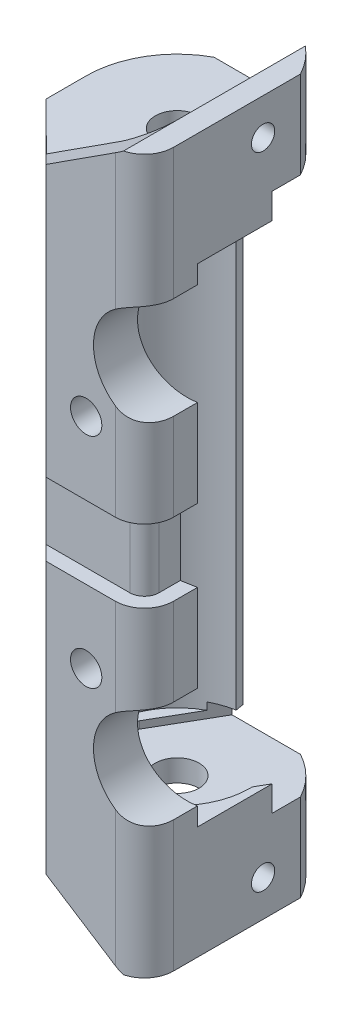
SolidWorks part; units mm, degrees
ref_plane "前视基准面" through (0, 0, 0) normal (0, 0, 1) x (1, 0, 0)
ref_plane "上视基准面" through (0, 0, 0) normal (0, 1, 0) x (1, 0, 0)
ref_plane "右视基准面" through (0, 0, 0) normal (1, 0, 0) x (0, 0, -1)
other "Configuration Table"
sketch "草图1" plane through (0, 0, 0) normal (0, 1, 0) x (1, 0, 0)
  line L0 (0, 12.5) -> (11, 12.5)
  line L1 (11, 12.5) -> (11, 10)
  line L3 (0, 10) -> (11, 10)
  line L6 (10, 0) -> (11, 0)
  line L7 (11, 0) -> (11, -5.9372)
  arc A0 (0, 10) -> (0, -10) centre (0, 0) ccw
  arc A1 (0, 12.5) -> (0, -12.5) centre (0, 0) ccw
  arc A2 (0, -12.5) -> (11, -5.9372) centre (0, 0) ccw
  arc A3 (0, -10) -> (10, 0) centre (0, 0) ccw
  dimension "D1" = 20
  dimension "D2" = 2.5
  dimension "D3" = 11
extrude "凸台-拉伸1" add sketch "草图1" along normal blind 80
sketch "草图2" plane through (0, 80, 0) normal (0, 1, 0) x (1, 0, 0)
  line L0 (-1.7365, 9.8481) -> (-2.1706, 12.3101)
  line L1 (0, 12.5) -> (0, 0) construction
  line L2 (0, 10) -> (11, 10) construction
  line L3 (11, 10) -> (11, 12.5) construction
  line L4 (11, 12.5) -> (0, 12.5) construction
  line L5 (0, 10) -> (11, 10)
  line L6 (11, 10) -> (11, 12.5)
  line L7 (11, 12.5) -> (0, 12.5)
  arc A0 (0, 10) -> (10, 0) centre (0, 0) ccw construction
  arc A1 (0, 12.5) -> (11, -5.9372) centre (0, 0) ccw construction
  arc A2 (0, 10) -> (-1.7365, 9.8481) centre (0, 0) ccw
  arc A3 (0, 12.5) -> (-2.1706, 12.3101) centre (0, 0) ccw
  dimension "D1" = 10
extrude "切除-拉伸1" cut sketch "草图2" against normal up to next
sketch "草图3" plane through (0, 80, 0) normal (0, 1, 0) x (1, 0, 0)
  line L0 (11, -5.9372) -> (11, 0) construction
  line L1 (-3.5, 12) -> (11, 12)
  line L2 (-3.5, 12) -> (-3.5, 12.5)
  line L3 (-3.5, 12.5) -> (11, 12.5)
  line L4 (11, 12) -> (11, 12.5)
  arc A0 (-2.1706, 12.3101) -> (11, -5.9372) centre (0, 0) ccw construction
  dimension "D1" = 12
extrude "切除-拉伸3" cut sketch "草图3" against normal up to next contours L1 L4 L3 L2
sketch "草图4" plane through (11, 0, 0) normal (1, 0, 0) x (0, 0, -1)
  line L0 (0, 0) -> (0, 89) construction
  line L1 (-5.9372, 80) -> (5.9372, 80)
  line L2 (-5.9372, 80) -> (-5.9372, 89)
  line L3 (-5.9372, 89) -> (5.9372, 89)
  line L4 (5.9372, 80) -> (5.9372, 89)
  line L5 (-12.5, 40) -> (12, 40) construction
  line L6 (-12.5, 80) -> (-12.5, 0) construction
  line L7 (12, 80) -> (12, 0) construction
  line L8 (5.9372, 0) -> (5.9372, -9)
  line L9 (-5.9372, -9) -> (5.9372, -9)
  line L10 (-5.9372, 0) -> (-5.9372, -9)
  line L11 (-5.9372, 0) -> (5.9372, 0)
  circle A0 centre (0.8, 84) radius 1.6
  circle A1 centre (0.8, -4) radius 1.6
  dimension "D2" = 3.2
  dimension "D3" = 88
  dimension "D4" = 0.8
  dimension "D1" = 98
extrude "凸台-拉伸2" add sketch "草图4" against normal blind 3
sketch "草图6" plane through (0, 0, 0) normal (0.9848, 0, -0.1736) x (-0.1736, 0, -0.9848)
  line L1 (-10, 73.5) -> (12.1851, 73.5)
  line L2 (-10, 73.5) -> (-10, 6.5)
  line L3 (-10, 6.5) -> (12.1851, 6.5)
  line L4 (12.1851, 73.5) -> (12.1851, 6.5)
  line L5 (12.1851, 80) -> (12.1851, 0) construction
  line L6 (-12.5, 40) -> (12.1851, 40) construction
  line L7 (-12.5, 80) -> (-12.5, 0) construction
  line L8 (10, 0) -> (10, 80) construction
  dimension "D1" = 67
  dimension "D2" = 20
extrude "切除-拉伸4" cut sketch "草图6" along normal up to next
sketch "草图7" plane through (8, 0, 0) normal (-1, 0, 0) x (0, 0, 1)
  circle A0 centre (-0.8, 84) radius 4 construction
  dimension "D1" = 8
sketch "草图8" plane through (11, 0, 0) normal (1, 0, 0) x (0, 0, -1)
  line L0 (-12.5, 80) -> (-12.5, 0) construction
  line L1 (-5.9372, 80) -> (-12.5, 80)
  line L2 (-5.9372, 80) -> (-5.9372, 0)
  line L3 (-5.9372, 0) -> (-12.5, 0)
  line L4 (-12.5, 80) -> (-12.5, 0)
extrude "凸台-拉伸5" add sketch "草图8" against normal up to surface up to face at (3.5589, 40, 4.8426)
sketch "草图9" plane through (0, 0, 12.5) normal (0, 0, 1) x (1, 0, 0)
  line L0 (11, 40) -> (-12.5, 40) construction
  line L1 (11, 80) -> (11, 0) construction
  line L2 (-12.5, 80) -> (-12.5, 0) construction
  circle A0 centre (11, 64) radius 7
  circle A1 centre (11, 16) radius 7
  dimension "D1" = 14
  dimension "D2" = 48
extrude "切除-拉伸5" cut sketch "草图9" against normal up to next
sketch "草图10" plane through (1.7365, 0, 9.8481) normal (-0.1736, 0, -0.9848) x (-0.9848, 0, 0.1736)
  line L0 (-9.8481, 6.5) -> (-10.8329, 6.5) construction
  line L1 (0, 73.5) -> (-10.3405, 73.5)
  line L2 (0, 73.5) -> (0, 6.5)
  line L3 (0, 6.5) -> (-10.3405, 6.5)
  line L4 (-10.3405, 73.5) -> (-10.3405, 6.5)
extrude "切除-拉伸6" cut sketch "草图10" along normal up to next
sketch "草图11" plane through (0, 0, 5.9372) normal (0, 0, 1) x (1, 0, 0)
  line L5 (11, 80) -> (11, 89)
  line L6 (11, 89) -> (8, 89)
  line L7 (8, 89) -> (8, 80)
  line L8 (8, 80) -> (8.0467, 80)
  line L9 (8.0467, 80) -> (11, 80)
  line L10 (11, 80) -> (11, 89)
  line L11 (11, 89) -> (8, 89)
  line L12 (8, 89) -> (8, 80)
  line L13 (8, 80) -> (8.0467, 80)
  line L14 (8.0467, 80) -> (11, 80)
  line L15 (11, -9) -> (11, 0)
  line L16 (11, 0) -> (8.0467, 0)
  line L17 (8.0467, 0) -> (8, 0)
  line L18 (8, 0) -> (8, -9)
  line L19 (8, -9) -> (11, -9)
  line L20 (11, -9) -> (11, 0)
  line L21 (11, 0) -> (8.0467, 0)
  line L22 (8.0467, 0) -> (8, 0)
  line L23 (8, 0) -> (8, -9)
  line L24 (8, -9) -> (11, -9)
  dimension "D1" = 0
  dimension "D2" = 0
extrude "凸台-拉伸6" add sketch "草图11" along normal up to surface (6.5628 mm away) up to face at (6.5, 40, 12.5)
sketch "草图12" plane through (0, 80, 0) normal (0, 1, 0) x (1, 0, 0)
  line L1 (0, -12.5) -> (11, -12.5)
  line L2 (11, -12.5) -> (11, 5.9372)
  line L3 (-3.5, 12) -> (3.5, 12)
  line L4 (-3.5, 12) -> (-2.1159, 12) construction
  arc A1 (11, 5.9372) -> (3.5, 12) centre (0, 0) ccw
  arc A2 (-3.5, 12) -> (0, -12.5) centre (0, 0) ccw
extrude "凸台-拉伸7" add sketch "草图12" against normal blind 3
sketch "草图13" plane through (0, 0, 0) normal (0, 0, -1) x (-1, 0, 0)
  line L4 (-10, 77) -> (-11, 77)
  line L5 (-11, 77) -> (-11, 73.5)
  line L6 (-11, 73.5) -> (-10, 73.5)
  line L7 (-10, 73.5) -> (-10, 77)
  line L8 (-10, 77) -> (-11, 77)
  line L9 (-11, 77) -> (-11, 73.5)
  line L10 (-11, 73.5) -> (-10, 73.5)
  line L11 (-10, 73.5) -> (-10, 77)
  line L12 (-10, 6.5) -> (-11, 6.5)
  line L13 (-11, 6.5) -> (-11, 0)
  line L14 (-11, 0) -> (-10, 0)
  line L15 (-10, 0) -> (-10, 6.5)
  line L16 (-10, 6.5) -> (-11, 6.5)
  line L17 (-11, 6.5) -> (-11, 0)
  line L18 (-11, 0) -> (-10, 0)
  line L19 (-10, 0) -> (-10, 6.5)
  dimension "D1" = 0
  dimension "D2" = 0
sketch "草图14" plane through (0, 77, 0) normal (0, -1, 0) x (1, 0, 0)
  line L0 (-7.3612, -4.25) -> (-4.7273, -8.8121)
  line L1 (7.3612, 4.25) -> (11, -2.0526)
  line L2 (11, 12.5) -> (11, -5.9372) construction
  line L4 (11, -5.9372) -> (11, 0)
  line L5 (11, 0) -> (10, 0)
  line L6 (-1.7365, -9.8481) -> (-2.1159, -12)
  line L7 (-2.1159, -12) -> (3.5, -12)
  line L8 (11, -2.0526) -> (11, 0)
  line L9 (11, 0) -> (10, 0)
  arc A0 (7.3612, 4.25) -> (-7.3612, -4.25) centre (0, 0) ccw
  arc A3 (10, 0) -> (-1.7365, -9.8481) centre (0, 0) ccw
  arc A4 (3.5, -12) -> (11, -5.9372) centre (0, 0) ccw
  arc A5 (10, 0) -> (-4.7273, -8.8121) centre (0, 0) ccw
  dimension "D1" = 17
  dimension "D3" = 30
  dimension "D2" = 0
extrude "凸台-拉伸9" add sketch "草图14" along normal blind 1
sketch "草图15" plane through (0, 77, 0) normal (0, -1, 0) x (1, 0, 0)
  line L0 (-4.7273, -8.8121) -> (-2.8868, -12)
  line L1 (-2.1159, -12) -> (-3.5, -12) construction
  line L2 (-4.7273, -8.8121) -> (-7.3612, -4.25) construction
  line L3 (-1.7365, -9.8481) -> (-2.1159, -12) construction
  line L4 (-2.1159, -12) -> (-2.8868, -12)
  line L5 (-1.7365, -9.8481) -> (-2.1159, -12)
  arc A0 (-4.7273, -8.8121) -> (-1.7365, -9.8481) centre (0, 0) ccw construction
  arc A1 (-4.7273, -8.8121) -> (-1.7365, -9.8481) centre (0, 0) ccw
extrude "切除-拉伸7" cut sketch "草图15" along normal blind 2
ref_plane "基准面1" through (-2.8868, 77, -12) normal (-0.5, 0, 0.866) x (0.866, 0, 0.5)
sketch "草图17" plane through (0, 0, 12.5) normal (0, 0, 1) x (1, 0, 0)
  line L1 (0, 80) -> (-12.5, 80)
  line L2 (0, 80) -> (0, 0)
  line L3 (0, 0) -> (-12.5, 0)
  line L4 (-12.5, 80) -> (-12.5, 0)
extrude "凸台-拉伸10" add sketch "草图17" against normal up to surface up to face at (-7.0622, 40, 1.0089)
sketch "草图16" plane through (-2.8868, 77, -12) normal (-0.5, 0, 0.866) x (0.866, 0, 0.5)
  line L0 (8.4641, -77) -> (8.4641, 3) construction
  line L1 (-1.5, -77) -> (18.4282, -77) construction
  line L2 (15.0577, 3) -> (5.5311, 3) construction
  line L4 (10.9641, 0) -> (5.9641, 0)
  line L5 (10.9641, 0) -> (10.9641, -4)
  line L6 (10.9641, -4) -> (5.9641, -4)
  line L7 (5.9641, 0) -> (5.9641, -4)
  line L8 (0, 0) -> (17, 0) construction
  dimension "D1" = 5
  dimension "D2" = 4
extrude "切除-拉伸8" cut sketch "草图16" along normal up to next
ref_plane "基准面2" through (0, 40, 0) normal (0, 1, 0) x (1, 0, 0)
mirror "镜向2" about plane through (0, 40, 0) normal (0, 1, 0) of "切除-拉伸8", "切除-拉伸7", "凸台-拉伸7", "凸台-拉伸10", "凸台-拉伸9"
extrude "凸台-拉伸11" add sketch "草图13" against normal up to surface (2.0526 mm away) contours L9 L10 L11 L8
sketch "草图18" plane through (0, 0, 12.5) normal (0, 0, 1) x (1, 0, 0)
  line L0 (8, 80) -> (8, 89)
  line L1 (8, 89) -> (-12.5, 80)
  line L2 (-12.5, 80) -> (8, 80)
  line L3 (-12.5, 0) -> (8, 0)
  line L4 (8, 0) -> (8, -9)
  line L5 (8, 0) -> (8, -9) construction
  line L6 (8, -9) -> (-12.5, 0)
extrude "凸台-拉伸12" add sketch "草图18" against normal blind 0.5
sketch "草图19" plane through (-2.8868, 77, -12) normal (-0.5, 0, 0.866) x (0.866, 0, 0.5)
  line L4 (10.9641, 0) -> (5.9641, 0)
  line L5 (10.9641, -4) -> (10.9641, 0)
  line L6 (5.9641, -4) -> (10.9641, -4)
  line L7 (5.9641, 0) -> (5.9641, -4)
  line L8 (10.9641, 0) -> (5.9641, 0)
  line L9 (10.9641, -4) -> (10.9641, 0)
  line L10 (5.9641, -4) -> (10.9641, -4)
  line L11 (5.9641, 0) -> (5.9641, -4)
  dimension "D1" = 0
extrude "切除-拉伸9" cut sketch "草图19" along normal up to next
sketch "草图20" plane through (0, 80, 0) normal (0, 1, 0) x (1, 0, 0)
  line L0 (-3.5, 12) -> (3.5, 12) construction
  line L1 (-5.9372, 11) -> (5.9372, 11)
  line L2 (-5.9372, 11) -> (-5.9372, 12)
  line L3 (-5.9372, 12) -> (5.9372, 12)
  line L4 (5.9372, 11) -> (5.9372, 12)
  arc A0 (-3.5, 12) -> (-12.5, 0) centre (0, 0) ccw construction
  arc A1 (11, 5.9372) -> (3.5, 12) centre (0, 0) ccw construction
  dimension "D1" = 11
extrude "切除-拉伸10" cut sketch "草图20" against normal up to next
sketch "草图21" plane through (0, 80, 0) normal (0, 1, 0) x (1, 0, 0)
  circle A0 centre (0, 0) radius 3
  dimension "D1" = 6
extrude "切除-拉伸11" cut sketch "草图21" against normal up to surface (80 mm away) up to face at (0.122, 0, -1.5927)
sketch "草图22" plane through (0, 0, 12.5) normal (0, 0, 1) x (1, 0, 0)
  line L0 (11, 40) -> (3, 40) construction
  line L1 (11, 57) -> (11, 23) construction
  line L2 (1.65, 40) -> (-1.65, 40) construction
  line L3 (3, 25) -> (3, 55) construction
  circle A0 centre (3, 55) radius 2.15
  circle A1 centre (3, 25) radius 2.15
  dimension "D1" = 4.3
  dimension "D2" = 8
  dimension "D3" = 15
extrude "切除-拉伸12" cut sketch "草图22" against normal up to next
sketch "草图24" plane through (0, 0, 12.5) normal (0, 0, 1) x (1, 0, 0)
  line L8 (11, 89) -> (8, 89)
  line L9 (8, 89) -> (-12.5, 80)
  line L10 (-12.5, 80) -> (-12.5, 0)
  line L11 (-12.5, 0) -> (8, -9)
  line L12 (8, -9) -> (11, -9)
  line L13 (11, -9) -> (11, 9)
  line L14 (11, 23) -> (11, 57)
  line L15 (11, 71) -> (11, 89)
  line L16 (11, 89) -> (8, 89)
  line L17 (8, 89) -> (-12.5, 80)
  line L18 (-12.5, 80) -> (-12.5, 0)
  line L19 (-12.5, 0) -> (8, -9)
  line L20 (8, -9) -> (11, -9)
  line L21 (11, -9) -> (11, 9)
  line L22 (11, 23) -> (11, 57)
  line L23 (11, 71) -> (11, 89)
  circle A0 centre (3, 25) radius 2.15 construction
  circle A1 centre (3, 55) radius 2.15 construction
  arc A2 (11, 23) -> (11, 9) centre (11, 16) ccw
  arc A3 (11, 71) -> (11, 57) centre (11, 64) ccw
  arc A4 (11, 23) -> (11, 9) centre (11, 16) ccw
  arc A5 (11, 71) -> (11, 57) centre (11, 64) ccw
  circle A6 centre (3, 25) radius 2.15
  circle A7 centre (3, 55) radius 2.15
  dimension "D1" = 0
extrude "凸台-拉伸13" add sketch "草图24" along normal blind 3
sketch "草图25" plane through (0, 0, 12.5) normal (0, 0, -1) x (-1, 0, 0)
  line L0 (4.3716, 73) -> (10.1451, 73) construction
  line L1 (10.1451, 73) -> (10.1451, 77) construction
  line L2 (10.1451, 77) -> (4.3716, 77) construction
  line L3 (4.3716, 77) -> (4.3716, 73) construction
  line L4 (10.1451, 7) -> (4.3716, 7) construction
  line L5 (4.3716, 7) -> (4.3716, 3) construction
  line L6 (4.3716, 3) -> (10.1451, 3) construction
  line L7 (10.1451, 3) -> (10.1451, 7) construction
  line L8 (4.3716, 73) -> (10.1451, 73)
  line L9 (10.1451, 73) -> (10.1451, 77)
  line L10 (10.1451, 77) -> (4.3716, 77)
  line L11 (4.3716, 77) -> (4.3716, 73)
  line L12 (10.1451, 7) -> (4.3716, 7)
  line L13 (4.3716, 7) -> (4.3716, 3)
  line L14 (4.3716, 3) -> (10.1451, 3)
  line L15 (10.1451, 3) -> (10.1451, 7)
extrude "切除-拉伸13" cut sketch "草图25" along direction (0.5, 0, -0.866) on the side against the normal up to next (3 mm away)
sketch "草图26" plane through (0, 0, 0) normal (0, -1, 0) x (1, 0, 0)
  line L0 (-2.5, 15.5) -> (-12.5, 5.5)
  line L1 (-12.5, 15.5) -> (8, 15.5) construction
  line L2 (-12.5, 0) -> (-12.5, 12) construction
  line L3 (-2.5, 15.5) -> (-12.5, 15.5)
  line L4 (-12.5, 15.5) -> (-12.5, 5.5)
  dimension "D1" = 10
extrude "切除-拉伸14" cut sketch "草图26" against normal up to next and the other way up to next
sketch "草图27" plane through (-9, 0, 9) normal (-0.7071, 0, 0.7071) x (0.7071, 0, 0.7071)
  line L0 (-4.9497, 40) -> (9.1924, 40) construction
  line L1 (-2.8787, 61) -> (7.1213, 61)
  line L2 (-2.8787, 61) -> (-2.8787, 19)
  line L3 (-2.8787, 19) -> (7.1213, 19)
  line L4 (7.1213, 61) -> (7.1213, 19)
  line L5 (-4.9497, 80) -> (-4.9497, 0) construction
  line L6 (9.1924, -4.3902) -> (9.1924, 84.3902) construction
  line L7 (2.1213, 40) -> (2.1213, 61) construction
  dimension "D1" = 10
  dimension "D2" = 42
fillet "圆角1" radius 4 5 edges at (11, 0, 15.5) (8, -4.5, 12) (8, 84.5, 12) (11, 40, 15.5) (11, 80, 15.5)
sketch "草图28" plane through (0, 0, 15.5) normal (0, 0, 1) x (1, 0, 0)
  line L0 (-12.5, 80) -> (-12.5, 0) construction
  line L1 (-12.5, 45) -> (11, 45)
  line L2 (-12.5, 45) -> (-12.5, 35)
  line L3 (-12.5, 35) -> (11, 35)
  line L4 (11, 45) -> (11, 35)
  line L5 (11, -9) -> (11, 9) construction
  line L6 (-12.5, 40) -> (11, 40) construction
  line L7 (1.65, 40) -> (-1.65, 40) construction
  dimension "D1" = 10
extrude "切除-拉伸16" cut sketch "草图28" against normal blind 2
sketch "草图29" plane through (0, 0, -5.9372) normal (0, 0, -1) x (-1, 0, 0)
  line L4 (-11, 89) -> (-11, 80)
  line L5 (-11, 80) -> (-8, 80)
  line L6 (-8, 80) -> (-8, 89)
  line L7 (-8, 89) -> (-11, 89)
  line L8 (-11, 89) -> (-11, 80)
  line L9 (-11, 80) -> (-8, 80)
  line L10 (-8, 80) -> (-8, 89)
  line L11 (-8, 89) -> (-11, 89)
  line L12 (-11, 0) -> (-11, -9)
  line L13 (-11, -9) -> (-8, -9)
  line L14 (-8, -9) -> (-8, 0)
  line L15 (-8, 0) -> (-11, 0)
  line L16 (-11, 0) -> (-11, -9)
  line L17 (-11, -9) -> (-8, -9)
  line L18 (-8, -9) -> (-8, 0)
  line L19 (-8, 0) -> (-11, 0)
  dimension "D1" = 0
  dimension "D2" = 0
extrude "凸台-拉伸14" add sketch "草图29" along normal up to surface (3.6675 mm away)
sketch "草图30" plane through (0, 0, 12) normal (0, 0, -1) x (-1, 0, 0)
  line L0 (-8, 89) -> (5.9372, 80)
  line L1 (5.9372, 80) -> (6, 82.8537)
  line L2 (6, 82.8537) -> (-8, 89)
  line L3 (6, 0) -> (-8, -9)
  line L4 (-8, -9) -> (6, -2.8537)
  line L5 (6, -2.8537) -> (6, 0)
extrude "切除-拉伸17" cut sketch "草图30" against normal up to next and the other way up to next
sketch "草图31" plane through (0, 0, 13.5) normal (0, 0, 1) x (1, 0, 0)
  line L0 (7, 45) -> (10.4641, 45) construction
  line L1 (9, 45) -> (11, 45)
  line L2 (9, 45) -> (9, 35)
  line L3 (9, 35) -> (11, 35)
  line L4 (11, 45) -> (11, 35)
  line L5 (11, 57) -> (11, 23) construction
  line L6 (-4.5, 35) -> (10.4641, 35) construction
  point P8 (9.3789, 35)
  dimension "D1" = 2
extrude "切除-拉伸18" cut sketch "草图31" against normal up to next
fillet "圆角2" radius 2 1 edges at (9, 40, 13.5)
sketch "草图32" plane through (0, 77, 0) normal (0, -1, 0) x (1, 0, 0)
  line L0 (0, 0) -> (-0.75, 1.299) construction
  line L1 (-7.3612, -4.25) -> (-8.1112, -2.951)
  line L2 (7.3612, 4.25) -> (6.6112, 5.549)
  line L3 (-4.7273, -8.8121) -> (-7.3612, -4.25) construction
  arc A0 (-7.3612, -4.25) -> (7.3612, 4.25) centre (0, 0) ccw
  arc A1 (6.6112, 5.549) -> (-8.1112, -2.951) centre (-0.75, 1.299) ccw
  arc A2 (-7.0327, 7.1092) -> (-4.7273, -8.8121) centre (0, 0) ccw construction
  point P3 (-0.375, 0.6495)
extrude "切除-拉伸19" cut sketch "草图32" along normal up to surface (74 mm away)
